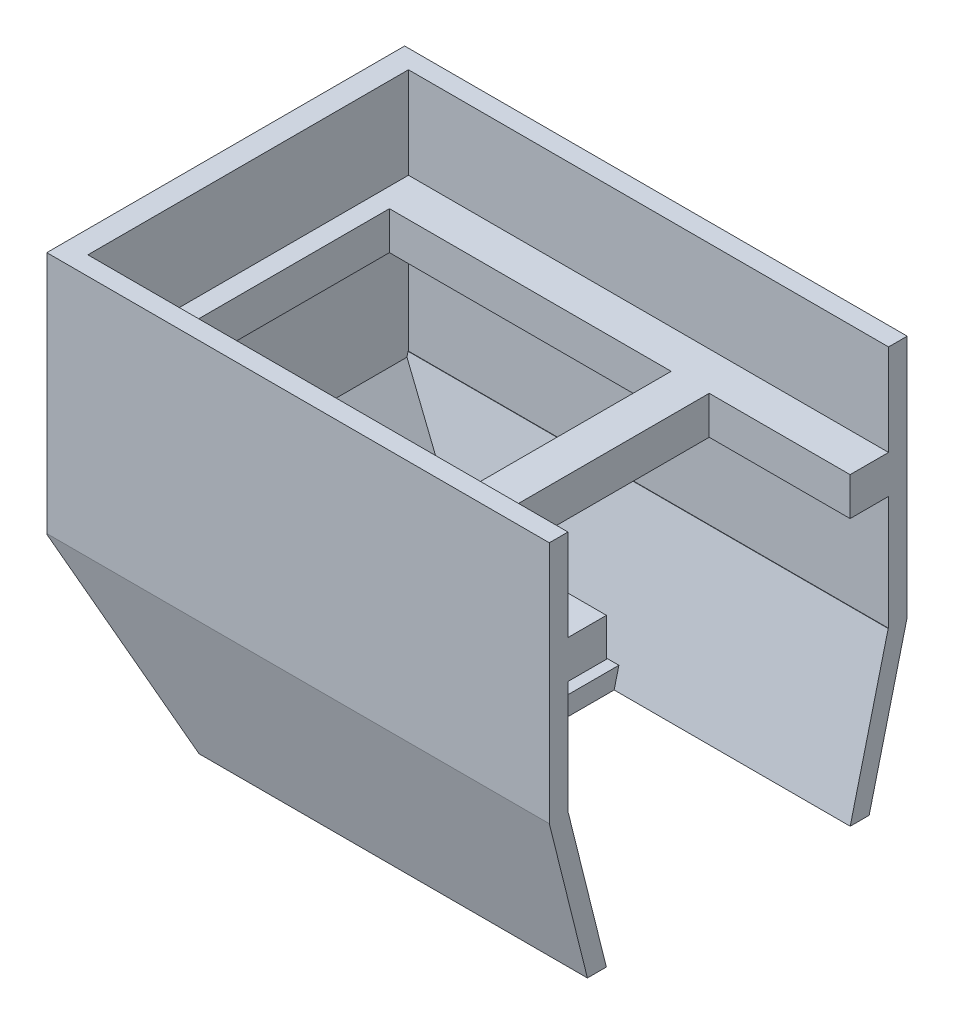
SolidWorks part; units mm, degrees
ref_plane "Front Plane" through (0, 0, 0) normal (0, 0, 1) x (1, 0, 0)
ref_plane "Top Plane" through (0, 0, 0) normal (0, 1, 0) x (1, 0, 0)
ref_plane "Right Plane" through (0, 0, 0) normal (1, 0, 0) x (0, 0, -1)
sketch "Sketch1" plane through (0, 0, 0) normal (0, 1, 0) x (1, 0, 0)
  line L0 (0, -51.7) -> (0, 51.7) construction
  line L1 (-126.1, 42.1) -> (126.1, 42.1)
  line L2 (-126.1, 42.1) -> (-126.1, -42.1)
  line L3 (-126.1, -42.1) -> (126.1, -42.1)
  line L4 (126.1, 42.1) -> (126.1, -42.1)
  line L5 (-37, 32) -> (37, 32)
  line L6 (-37, 32) -> (-37, -32)
  line L7 (-131, 47) -> (131, 47)
  line L8 (-131, 47) -> (-131, -47)
  line L9 (-131, -47) -> (131, -47)
  line L10 (131, 47) -> (131, -47)
  line L11 (-37, -32) -> (37, -32)
  line L12 (37, 32) -> (37, -32)
  line L15 (37, -42.1) -> (47, -42.1)
  line L16 (37, -32) -> (37, 42.1)
  line L17 (37, 42.1) -> (47, 42.1)
  line L18 (47, -32) -> (47, 42.1)
  line L19 (47, -32) -> (121, -32)
  line L20 (47, -32) -> (47, 32)
  line L21 (47, 32) -> (121, 32)
  line L22 (121, -32) -> (121, 32)
  line L23 (-37, 32) -> (-37, -32)
  line L24 (37, 32) -> (37, -32)
  line L25 (-47, 32) -> (-121, 32)
  line L26 (-121, -32) -> (-121, 32)
  line L27 (-47, -32) -> (-121, -32)
  line L28 (-47, -32) -> (-47, 32)
  line L29 (-37, 42.1) -> (-47, 42.1)
  line L30 (-47, -32) -> (-47, 32)
  line L31 (-37, -42.1) -> (-47, -42.1)
  line L32 (-37, -32) -> (-37, 32)
  point P0 (0, 0)
  point P6 (0, 0)
  point P11 (0, 0)
  dimension "D1" = 252.2
  dimension "D2" = 84.2
  dimension "D3" = 262
  dimension "D4" = 94
  dimension "D5" = 74
  dimension "D6" = 64
  dimension "D7" = 10
  dimension "D8" = 74
  dimension "D9" = 5.1
extrude "Boss-Extrude3" add sketch "Sketch1" along normal blind 10
sketch "Sketch3" plane through (0, 10, 0) normal (0, 1, 0) x (1, 0, 0)
  line L1 (-126.1, 42.1) -> (126.1, 42.1)
  line L2 (-126.1, 42.1) -> (-126.1, -42.1)
  line L3 (-126.1, -42.1) -> (126.1, -42.1)
  line L4 (126.1, 42.1) -> (126.1, -42.1)
  line L5 (-126.1, 42.1) -> (126.1, -42.1) construction
  line L6 (-126.1, -42.1) -> (126.1, 42.1) construction
  line L7 (-132, 47) -> (132, 47)
  line L8 (-132, 47) -> (-132, -47)
  line L9 (-132, -47) -> (132, -47)
  line L10 (132, 47) -> (132, -47)
  line L11 (-132, 47) -> (132, -47) construction
  line L12 (-132, -47) -> (132, 47) construction
  point P0 (0, 0)
  point P7 (0, 0)
  dimension "D1" = 264
  dimension "D2" = 94
extrude "Boss-Extrude4" add sketch "Sketch3" along normal blind 24 and the other way blind 80
sketch "Sketch4" plane through (0, -70, 0) normal (0, -1, 0) x (-1, 0, 0)
  line L4 (97, -32) -> (97, 32)
  line L8 (97, 32) -> (-97, 32)
  line L14 (-97, -32) -> (-97, 32)
  line L17 (97, -32) -> (-97, -32)
  line L19 (132, -47) -> (-132, -47)
  line L20 (132, -47) -> (132, 47)
  line L21 (132, 47) -> (-132, 47)
  line L22 (-132, -47) -> (-132, 47)
extrude "Boss-Extrude5" add sketch "Sketch4" against normal blind 40
ref_plane "Plane23" through (0, -30, 0) normal (0, -1, 0) x (-1, 0, 0)
chamfer "Chamfer4" distance 30 angle 53 2 edges at (-97, -30, 0) (-132, -70, 0)
chamfer "Chamfer7" distance 30 angle 53 2 edges at (97, -30, 0) (132, -70, 0)
chamfer "Chamfer8" distance 10 angle 76 2 edges at (0, -30, -32) (0, -70, -47)
chamfer "Chamfer9" distance 10 angle 76 2 edges at (0, -30, 32) (0, -70, 47)
ref_plane "Plane28" through (0, 0, 0) normal (1, 0, 0) x (0, 0, -1)
split "Split1" trim tools "Plane28" bodies to split 105 resulting bodies 107
ref_plane "Plane29" through (0, -65, 0) normal (0, -1, 0) x (-1, 0, 0)
sketch "Sketch7" plane through (0, -65, 0) normal (0, -1, 0) x (-1, 0, 0)
  line L1 (0, -37) -> (102, -37) construction
  line L2 (72, -37) -> (72, 37)
  line L3 (102, 37) -> (0, 37) construction
  line L6 (72, -37) -> (62, -37)
  line L7 (62, -37) -> (62, 37)
  line L8 (62, 37) -> (72, 37)
  line L9 (102, -37) -> (102, 37) construction
  dimension "D1" = 10
  dimension "D2" = 30
extrude "Boss-Extrude6" add sketch "Sketch7" along normal up to surface (5 mm away) up to face at (-49.75, -70, 0)
